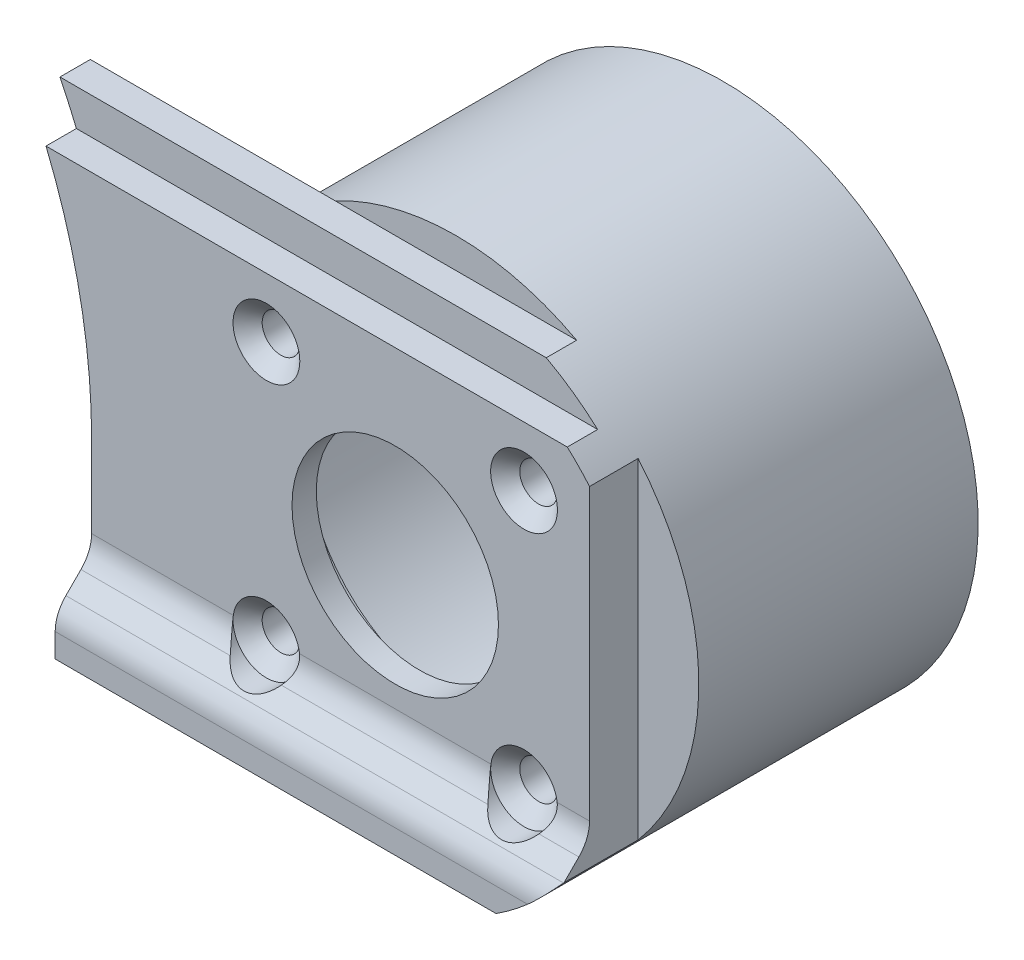
SolidWorks part; units mm, degrees
note: The reader was unsure of these and kept them because the rebuilt part matched: shared geometry of "Szkic8<3>".
ref_plane "Płaszczyzna przednia" through (0, 0, 0) normal (0, 0, 1) x (1, 0, 0)
ref_plane "Płaszczyzna górna" through (0, 0, 0) normal (0, 1, 0) x (1, 0, 0)
ref_plane "Płaszczyzna prawa" through (0, 0, 0) normal (1, 0, 0) x (0, 0, -1)
sketch "Szkic1" plane through (0, 0, 0) normal (0, 0, 1) x (1, 0, 0)
  line L1 (-44, 15.5) -> (16, 15.5)
  line L2 (-44, 15.5) -> (-44, -15.5)
  line L3 (-44, -15.5) -> (16, -15.5)
  line L4 (16, 15.5) -> (16, -15.5)
  circle A0 centre (0, 0) radius 12.5
  point P8 (16, 0)
  dimension "D1" = 25
  dimension "D4" = 16
  dimension "D2" = 31
  dimension "D3" = 60
extrude "Dodanie-wyciągnięcie1" add sketch "Szkic1" along normal blind 5 contours L4 L1 L2 L3 A0
sketch "Szkic11" plane through (0, 0, 5) normal (0, 0, 1) x (1, 0, 0)
  circle A0 centre (0, 0) radius 8.5
  circle A1 centre (0, 0) radius 12.5 construction
  circle A2 centre (0, 0) radius 12.5
  dimension "D1" = 17
extrude "Dodanie-wyciągnięcie5" add sketch "Szkic11" against normal blind 2
sketch "Szkic7" plane through (-44, 0, 0) normal (-1, 0, 0) x (0, 0, 1)
  line L0 (5, 15.5) -> (0, 15.5) construction
  line L1 (0, 18.5) -> (2.5, 18.5)
  line L2 (0, 18.5) -> (0, 15.5)
  line L3 (0, 15.5) -> (2.5, 15.5)
  line L4 (2.5, 18.5) -> (2.5, 15.5)
  line L5 (5, 15.5) -> (5, -15.5) construction
  line L6 (0, -15.5) -> (2.5, -15.5)
  line L7 (0, -15.5) -> (0, -18.5)
  line L8 (0, -18.5) -> (2.5, -18.5)
  line L9 (2.5, -15.5) -> (2.5, -18.5)
  line L11 (5, -11.5) -> (5, -17.7036)
  line L12 (5, -17.7036) -> (8, -17.7036)
  line L14 (70, -17.7036) -> (5, -17.7036) construction
  line L16 (8, -14.5) -> (5, -11.5)
  line L17 (5, -17.7036) -> (5, 11) construction
  line L18 (8, -14.5) -> (8, -17.7036)
  line L19 (5, -15.5) -> (0, -15.5) construction
  dimension "D1" = 3
  dimension "D2" = 2.5
  dimension "D3" = 3
  dimension "D4" = 45
  dimension "D5" = 4
extrude "Dodanie-wyciągnięcie3" add sketch "Szkic7" against normal through all
fillet "Zaokrąglenie1" radius 3 2 edges at (-14, -14.5, 8) (-14, -11.5, 5)
sketch "Szkic2" plane through (0, 0, 5) normal (0, 0, 1) x (1, 0, 0)
  line L1 (-25, -3.5142) -> (-25, -20.5)
  line L5 (-44, 35.7159) -> (-44, -20.5)
  line L6 (-44, 15.5) -> (-44, -10.2574) construction
  line L7 (-44, -20.5) -> (-25, -20.5)
  line L8 (-44, -15.5) -> (16, -15.5) construction
  arc A1 (-25, -3.5142) -> (-44, 35.7159) centre (-75, -3.5142) ccw
  dimension "D1" = 50
  dimension "D2" = 25
  dimension "D3" = 75
  dimension "D4" = 3.5142
  dimension "D5" = 5
extrude "Wytnij-wyciągnięcie1" cut sketch "Szkic2" against normal through all and the other way through all
sketch "Szkic3" plane through (0, 0, 0) normal (0, 0, -1) x (-1, 0, 0)
  circle A0 centre (0, 0) radius 18
  circle A1 centre (0, 0) radius 21
  dimension "D1" = 36
  dimension "D2" = 42
extrude "Dodanie-wyciągnięcie2" add sketch "Szkic3" along normal blind 22
sketch "Szkic4" plane through (0, 0, 5) normal (0, 0, 1) x (1, 0, 0)
  line L0 (10.2491, -10.2491) -> (-11.5615, 11.5615) construction
  line L1 (0.9741, 0.9741) -> (18.0256, 18.0256) construction
  line L3 (-15, 0) -> (15, 0) construction
  circle A0 centre (0, 0) radius 15 construction
  point P4 (-10.6066, 10.6066)
  point P8 (10.6066, 10.6066)
  point P9 (10.6066, -10.6066)
  point P10 (-10.6066, -10.6066)
  dimension "D1" = 30
  dimension "D2" = 45
hole_wizard "Pogłębienie stożkowe pod M2.5 Śrubę z łbem soczewkowym1" positions "Szkic5" profile "Szkic6" countersink size "M2.5" standard "ISO"
sketch "Szkic5" plane through (0, 0, 5) normal (0, 0, 1) x (1, 0, 0)
  point P0 (-10.6066, 10.6066)
  point P3 (-10.6066, -10.6066)
  point P6 (10.6066, -10.6066)
  point P9 (10.6066, 10.6066)
sketch "Szkic6" plane through (-10.6066, 10.6066, 5) normal (1, 0, 0) x (0, -1, 0)
  line L0 (0, 0) -> (0, 27)
  line L1 (0, 27) -> (1.55, 27)
  line L2 (1.55, 27) -> (1.55, 1.2)
  line L3 (1.55, 1.2) -> (2.75, 0)
  line L5 (2.75, 0) -> (0, 0)
  line L6 (-1.55, 1.2) -> (-2.75, 0) construction
  line L11 (0, -6.35) -> (0, 107.95) construction
  dimension "Średnica otworu na wylot" = 3.1
  dimension "Głębokość otworu na wylot" = 27
  dimension "Średnica zewnętrznego pogłębienia stożkowego" = 5.5
  dimension "Kąt zewnętrznego pogłębienia stożkowego" = 90
sketch "Szkic15" plane through (0, 0, 5) normal (0, 0, 1) x (1, 0, 0)
  arc A2 (-13.3343, -10.2574) -> (-7.8789, -10.2574) centre (-10.6066, -10.6066) ccw
  arc A3 (-7.8789, -10.2574) -> (-13.3343, -10.2574) centre (-10.6066, -10.6066) ccw
  arc A4 (-13.3343, -10.2574) -> (-7.8789, -10.2574) centre (-10.6066, -10.6066) ccw
  arc A5 (-7.8789, -10.2574) -> (-13.3343, -10.2574) centre (-10.6066, -10.6066) ccw
  arc A6 (7.8789, -10.2574) -> (13.3343, -10.2574) centre (10.6066, -10.6066) ccw
  arc A7 (13.3343, -10.2574) -> (7.8789, -10.2574) centre (10.6066, -10.6066) ccw
  arc A8 (7.8789, -10.2574) -> (13.3343, -10.2574) centre (10.6066, -10.6066) ccw
  arc A9 (13.3343, -10.2574) -> (7.8789, -10.2574) centre (10.6066, -10.6066) ccw
  dimension "D1" = 0
  dimension "D2" = 0
extrude "Wytnij-wyciągnięcie3" cut sketch "Szkic15" along normal through all
sketch "Szkic8" plane through (0, 0, 0) normal (0, 0, 1) x (1, 0, 0)
  line L0 (16, -13.6015) -> (16, -18.5) construction
  line L1 (16, -18.5) -> (9.9373, -18.5) construction
  line L3 (16, 8.2462) -> (16, -8.2462) construction
  line L5 (9.9373, 18.5) -> (16, 18.5) construction
  line L6 (16, 18.5) -> (16, 13.6015) construction
  line L7 (16, -13.6015) -> (16, -18.5)
  line L8 (16, -18.5) -> (9.9373, -18.5)
  line L9 (9.9373, 18.5) -> (16, 18.5)
  line L10 (16, 18.5) -> (16, 13.6015)
  line L11 (16, 13.6015) -> (16, -13.6015)
  line L13 (16, 13.6015) -> (16, 8.2462)
  line L14 (16, -8.2462) -> (16, -13.6015)
  arc A0 (9.9373, -18.5) -> (16, -13.6015) centre (0, 0) ccw construction
  arc A1 (16, 13.6015) -> (9.9373, 18.5) centre (0, 0) ccw construction
  arc A5 (9.9373, -18.5) -> (16, -13.6015) centre (0, 0) ccw
  arc A6 (16, 13.6015) -> (9.9373, 18.5) centre (0, 0) ccw
  arc A9 (16, -13.6015) -> (16, 13.6015) centre (0, 0) ccw
  arc A10 (16, -8.2462) -> (16, 8.2462) centre (0, 0) ccw
  arc A11 (16, -13.6015) -> (16, 13.6015) centre (0, 0) ccw
  dimension "D1" = 0
extrude "Dodanie-wyciągnięcie4" add sketch "Szkic8" along normal blind 1 contours L11 A11
extrude "Wytnij-wyciągnięcie2" cut sketch "Szkic8<3>" along normal through all contours A6 L10 L9 | A5 L8 L7
sketch "Szkic8<3>" plane through (0, 0, 0) normal (0, 0, 1) x (1, 0, 0) same geometry as "Szkic8"
